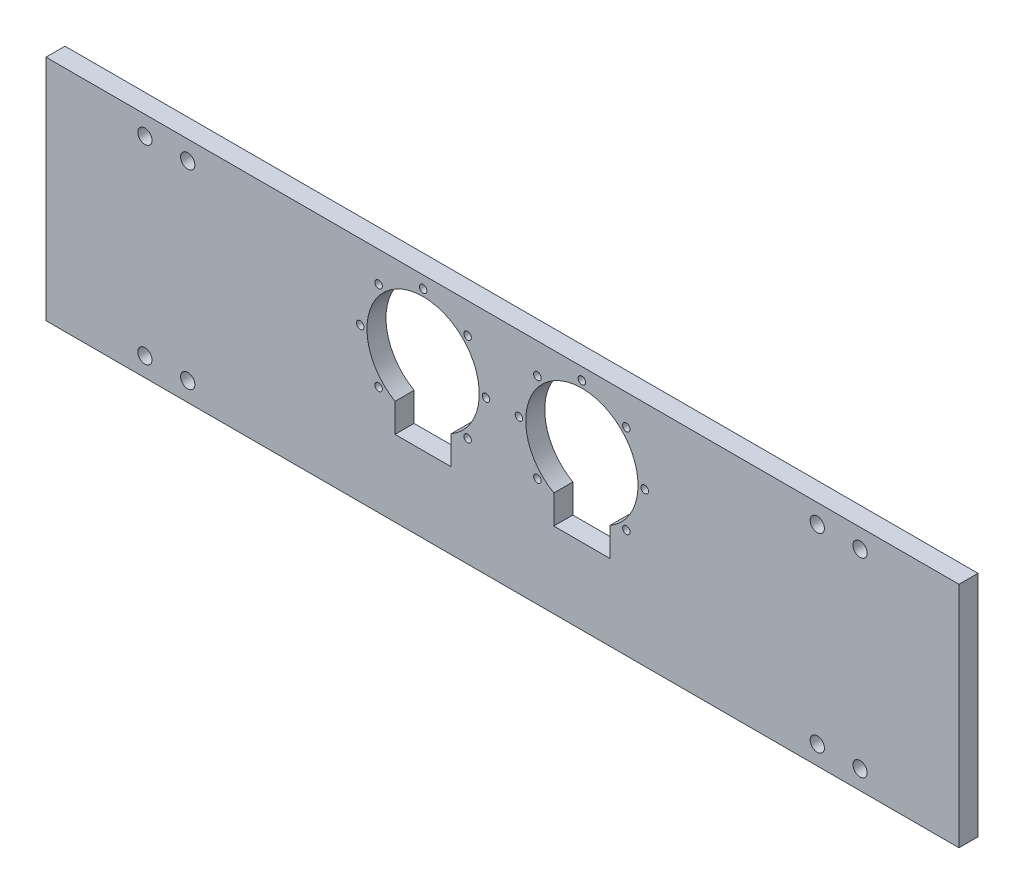
SolidWorks part; units mm, degrees
ref_plane "Front Plane" through (0, 0, 0) normal (0, 0, 1) x (1, 0, 0)
ref_plane "Top Plane" through (0, 0, 0) normal (0, 1, 0) x (1, 0, 0)
ref_plane "Right Plane" through (0, 0, 0) normal (1, 0, 0) x (0, 0, -1)
sketch "Sketch1" plane through (0, 0, 0) normal (0, 0, 1) x (1, 0, 0)
  line L0 (-304.8, 0) -> (304.8, 0) construction
  line L1 (-304.8, 76.2) -> (304.8, 76.2)
  line L2 (-304.8, 76.2) -> (-304.8, -76.2)
  line L3 (-304.8, -76.2) -> (304.8, -76.2)
  line L4 (304.8, 76.2) -> (304.8, -76.2)
  line L5 (-304.8, 76.2) -> (304.8, -76.2) construction
  line L6 (-304.8, -76.2) -> (304.8, 76.2) construction
  line L7 (0, 76.2) -> (0, -76.2) construction
  line L8 (53, 26.2) -> (53, -11.3) construction
  line L9 (53, 26.2) -> (34.25, -6.276) construction
  line L10 (53, 26.2) -> (71.75, -6.276) construction
  line L11 (34.25, -6.276) -> (34.25, -25.4)
  line L12 (71.75, -6.276) -> (71.75, -25.4)
  line L13 (71.75, -25.4) -> (34.25, -25.4)
  line L14 (238.76, 76.2) -> (238.76, -76.2) construction
  line L15 (210.185, 76.2) -> (210.185, -76.2) construction
  line L16 (-34.25, -6.276) -> (-34.25, -25.4)
  line L17 (-71.75, -25.4) -> (-34.25, -25.4)
  line L18 (-71.75, -6.276) -> (-71.75, -25.4)
  circle A5 centre (53, 26.2) radius 48 construction
  arc A6 (71.75, -6.276) -> (34.25, -6.276) centre (53, 26.2) ccw
  circle A7 centre (53, 26.2) radius 42 construction
  circle A8 centre (53, 68.2) radius 2.5
  circle A9 centre (82.6985, 55.8985) radius 2.5
  circle A10 centre (95, 26.2) radius 2.5
  circle A11 centre (82.6985, -3.4985) radius 2.5
  circle A13 centre (23.3015, -3.4985) radius 2.5
  circle A14 centre (11, 26.2) radius 2.5
  circle A15 centre (23.3015, 55.8985) radius 2.5
  arc A16 (55.4993, -15.7405) -> (50.5007, -15.7405) centre (53, -15.8) ccw [skipped]
  circle A17 centre (238.76, 63.5) radius 4.7625
  circle A18 centre (210.185, 63.5) radius 4.7625
  circle A19 centre (238.76, -63.5) radius 4.7625
  circle A20 centre (210.185, -63.5) radius 4.7625
  circle A21 centre (-82.6985, -3.4985) radius 2.5
  circle A22 centre (-95, 26.2) radius 2.5
  circle A23 centre (-82.6985, 55.8985) radius 2.5
  circle A24 centre (-53, 68.2) radius 2.5
  circle A25 centre (-23.3015, 55.8985) radius 2.5
  circle A26 centre (-11, 26.2) radius 2.5
  circle A27 centre (-23.3015, -3.4985) radius 2.5
  arc A28 (-71.75, -6.276) -> (-34.25, -6.276) centre (-53, 26.2) cw
  circle A29 centre (-238.76, 63.5) radius 4.7625
  circle A30 centre (-210.185, 63.5) radius 4.7625
  circle A31 centre (-210.185, -63.5) radius 4.7625
  circle A32 centre (-238.76, -63.5) radius 4.7625
  point P0 (0, 0)
  point P32 (53, 26.2)
  dimension "D3" = 96
  dimension "D6" = 75
  dimension "D7" = 84
  dimension "D8" = 5
  dimension "D15" = 9.525
  dimension "D17" = 9.525
  dimension "D1" = 609.6
  dimension "D2" = 152.4
  dimension "D4" = 53
  dimension "D5" = 50
  dimension "D10" = 30
  dimension "D11" = 30
  dimension "D12" = 50.8
  dimension "D13" = 66.04
  dimension "D14" = 28.575
  dimension "D16" = 12.7
  dimension "D18" = 12.7
  dimension "D9" = 8
extrude "Boss-Extrude1" add sketch "Sketch1" along normal blind 12.7
equation "\"bplate_length\"= 24in"
equation "\"bplate_height\"= 6in"
equation "\"bplate_thickness\"= 0.5in"
equation "\"motor_diameter\"= 96 / 25.4in"
equation "\"motor_clearance\"= 5 / 25.4in"
equation "\"motor_mount_hole_pattern_dia\"= 84 / 25.4in"
equation "\"motor_mount_hole_dia\"= 5 / 25.4in"
equation "\"motor_cx\"= \"motor_clearance\" + \"motor_diameter\" / 2in"
equation "\"motor_cy_top\"= \"motor_mount_hole_pattern_dia\" / 2 + \"motor_mount_hole_dia\" * 2in"
equation "\"D1@Sketch1\"=\"bplate_length\""
equation "\"D2@Sketch1\"=\"bplate_height\""
equation "\"motor_driver_cover_dia\"= 75 / 25.4in"
equation "\"D4@Sketch1\"=\"motor_cx\""
equation "\"motor_driver_cutout_clearance\"= 60deg"
equation "\"wire_cutout_clearance\"= 2in"
equation "\"connector_plate_thickness\"= 1in"
equation "\"connector_plate_hole_diameter\"= 0.375in"
equation "\"connector_plate_hole_depth\"= 1in"
equation "\"coonector_first_hole_offset\"= 1.6in"
equation "\"D14@Sketch1\"=\"connector_plate_hole_diameter\"*3in"
equation "\"D13@Sketch1\"=\"coonector_first_hole_offset\"+1in"
equation "\"D12@Sketch1\"=\"wire_cutout_clearance\""
equation "\"D16@Sketch1\"=\"connector_plate_thickness\"/2"
equation "\"D18@Sketch1\"=\"connector_plate_thickness\"/2"
equation "\"D15@Sketch1\"=\"connector_plate_hole_diameter\""
equation "\"D17@Sketch1\"=\"connector_plate_hole_diameter\""
equation "\"D8@Sketch1\"=\"motor_mount_hole_dia\""
equation "\"D6@Sketch1\"=\"motor_driver_cover_dia\""
equation "\"D7@Sketch1\"=\"motor_mount_hole_pattern_dia\""
